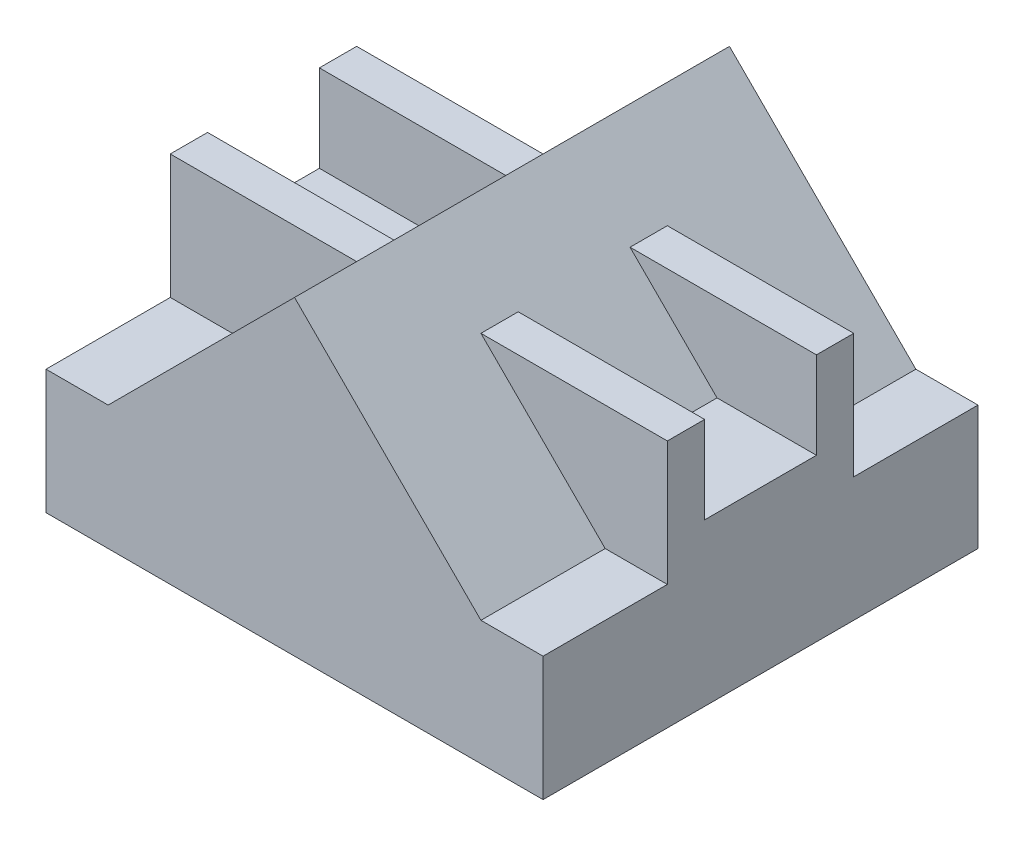
SolidWorks part; units mm, degrees
ref_plane "Front Plane" through (0, 0, 0) normal (0, 0, 1) x (1, 0, 0)
ref_plane "Top Plane" through (0, 0, 0) normal (0, 1, 0) x (1, 0, 0)
ref_plane "Right Plane" through (0, 0, 0) normal (1, 0, 0) x (0, 0, -1)
sketch "Sketch1" plane through (0, 0, 0) normal (0, 0, 1) x (1, 0, 0)
  line L0 (-100, -12.5) -> (100, -12.5)
  line L1 (-100, -62.5) -> (100, -62.5)
  line L2 (-100, -62.5) -> (-100, 62.5)
  line L3 (-100, 62.5) -> (100, 62.5)
  line L4 (100, -62.5) -> (100, 62.5)
  line L5 (-100, -62.5) -> (100, 62.5) construction
  line L6 (-100, 62.5) -> (100, -62.5) construction
  line L7 (-100, 37.5) -> (100, 37.5)
  line L8 (-75, -12.5) -> (0, 62.5)
  line L9 (0, 62.5) -> (75, -12.5)
  line L10 (0, 62.5) -> (0, -12.5) construction
  point P0 (0, 0)
  point P12 (0, 0)
  dimension "D1" = 125
  dimension "D2" = 200
  dimension "D3" = 50
  dimension "D4" = 100
extrude "Boss-Extrude1" add sketch "Sketch1" along normal blind 175 contours L1 L4 L0 L2 | L9 L7 L8 L0 | L9 L8 L7 | L7 L9 L0 L4 | L3 L9 L7 L4 | L7 L8 L3 L2 | L0 L8 L7 L2 region at (-72.9167, 16.6667, 0) region at (0, -37.5, 0) region at (0, 8.3333, 0) region at (-55.9524, 50.5952, 0) region at (72.9167, 16.6667, 0) region at (0, 45.8333, 0) region at (55.9524, 50.5952, 0)
extrude "Cut-Extrude1" cut sketch "Sketch1<3>" along normal through all contours L3 L9 L7 L4 | L7 L8 L3 L2 region at (-55.9524, 50.5952, 0) region at (55.9524, 50.5952, 0)
sketch "Sketch1<3>" plane through (0, 0, 0) normal (0, 0, 1) x (1, 0, 0) same geometry as "Sketch1"
extrude "Cut-Extrude2" cut sketch "Sketch1<4>" along normal through all contours L0 L8 L7 L2 | L7 L9 L0 L4 region at (-72.9167, 16.6667, 0) region at (72.9167, 16.6667, 0)
sketch "Sketch1<4>" plane through (0, 0, 0) normal (0, 0, 1) x (1, 0, 0) same geometry as "Sketch1"
extrude "Boss-Extrude2" add sketch "Sketch1<5>" along normal blind 125 contours L0 L8 L7 L2 | L7 L9 L0 L4 region at (-72.9167, 16.6667, 0) region at (72.9167, 16.6667, 0)
sketch "Sketch1<5>" plane through (0, 0, 0) normal (0, 0, 1) x (1, 0, 0) same geometry as "Sketch1"
extrude "Cut-Extrude3" cut sketch "Sketch1<6>" along normal blind 110 contours L0 L8 L7 L2 | L7 L9 L0 L4 region at (-72.9167, 16.6667, 0) region at (72.9167, 16.6667, 0)
sketch "Sketch1<6>" plane through (0, 0, 0) normal (0, 0, 1) x (1, 0, 0) same geometry as "Sketch1"
extrude "Boss-Extrude3" add sketch "Sketch1<9>" along normal blind 65 contours L7 L9 L0 L4 | L0 L8 L7 L2 region at (-72.9167, 16.6667, 0) region at (72.9167, 16.6667, 0)
sketch "Sketch1<9>" plane through (0, 0, 0) normal (0, 0, 1) x (1, 0, 0) same geometry as "Sketch1"
extrude "Cut-Extrude4" cut sketch "Sketch1<10>" along normal blind 50 contours L7 L9 L0 L4 | L0 L8 L7 L2 region at (-72.9167, 16.6667, 0) region at (72.9167, 16.6667, 0)
sketch "Sketch1<10>" plane through (0, 0, 0) normal (0, 0, 1) x (1, 0, 0) same geometry as "Sketch1"
sketch "Sketch3" plane through (0, -12.5, 0) normal (0, 1, 0) x (1, 0, 0)
  line L1 (-100, -65) -> (100, -65)
  line L2 (-100, -65) -> (-100, -110)
  line L3 (-100, -110) -> (100, -110)
  line L4 (100, -65) -> (100, -110)
extrude "Boss-Extrude4" add sketch "Sketch3" along normal blind 15
